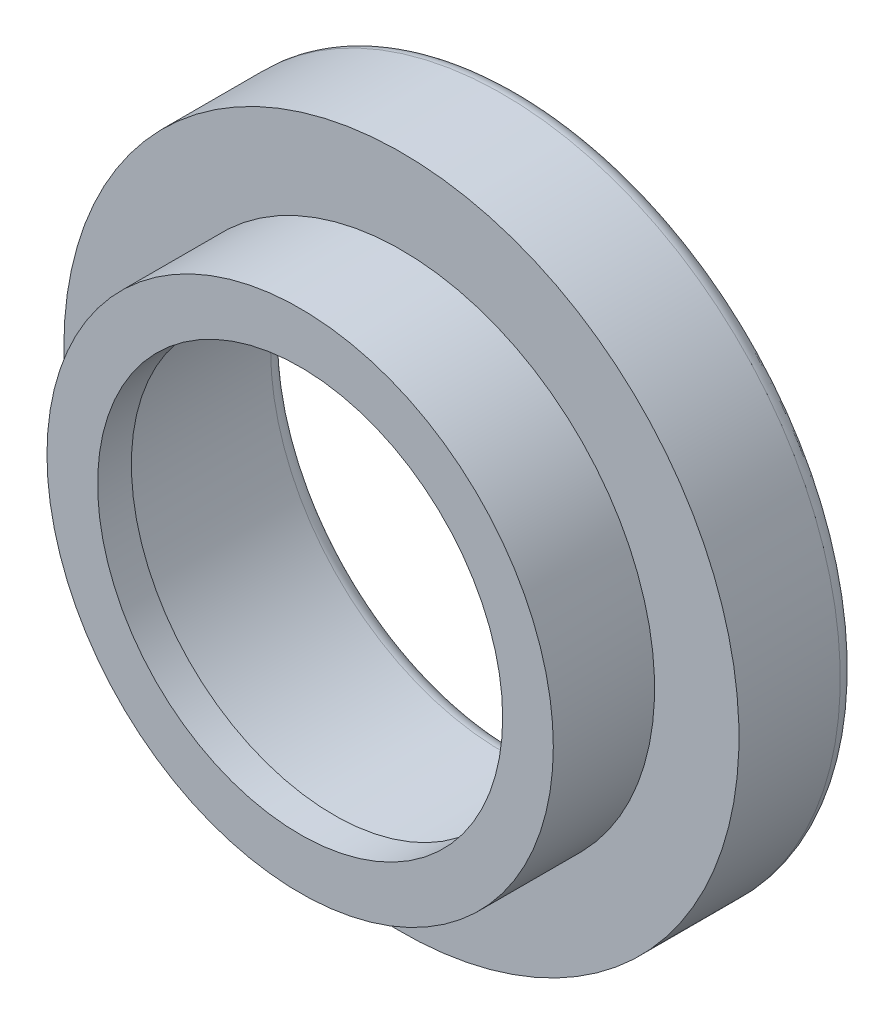
SolidWorks part; units mm, degrees
ref_plane "前视基准面" through (0, 0, 0) normal (0, 0, 1) x (1, 0, 0)
ref_plane "上视基准面" through (0, 0, 0) normal (0, 1, 0) x (1, 0, 0)
ref_plane "右视基准面" through (0, 0, 0) normal (1, 0, 0) x (0, 0, -1)
sketch "草图1" plane through (0, 0, 0) normal (0, 0, 1) x (1, 0, 0)
  circle A0 centre (0, 0) radius 15
  circle A1 centre (0, 0) radius 13.75
  dimension "D1" = 27.5
  dimension "D2" = 30
extrude "凸台-拉伸1" add sketch "草图1" along normal blind 4
sketch "草图2" plane through (0, 0, 4) normal (0, 0, 1) x (1, 0, 0)
  circle A0 centre (0, 0) radius 15 construction
  circle A1 centre (0, 0) radius 12
  circle A2 centre (0, 0) radius 15
  dimension "D1" = 24
extrude "凸台-拉伸2" add sketch "草图2" along normal blind 2
sketch "草图3" plane through (0, 0, 0) normal (0, 0, -1) x (-1, 0, 0)
  circle A0 centre (0, 0) radius 20
  circle A1 centre (0, 0) radius 13.75
  dimension "D1" = 40
extrude "凸台-拉伸3" add sketch "草图3" along normal blind 7
fillet "圆角1" radius 1 1 edges at (-13.75, 0, -7)
fillet "圆角2" radius 1 1 edges at (-20, 0, -7)
